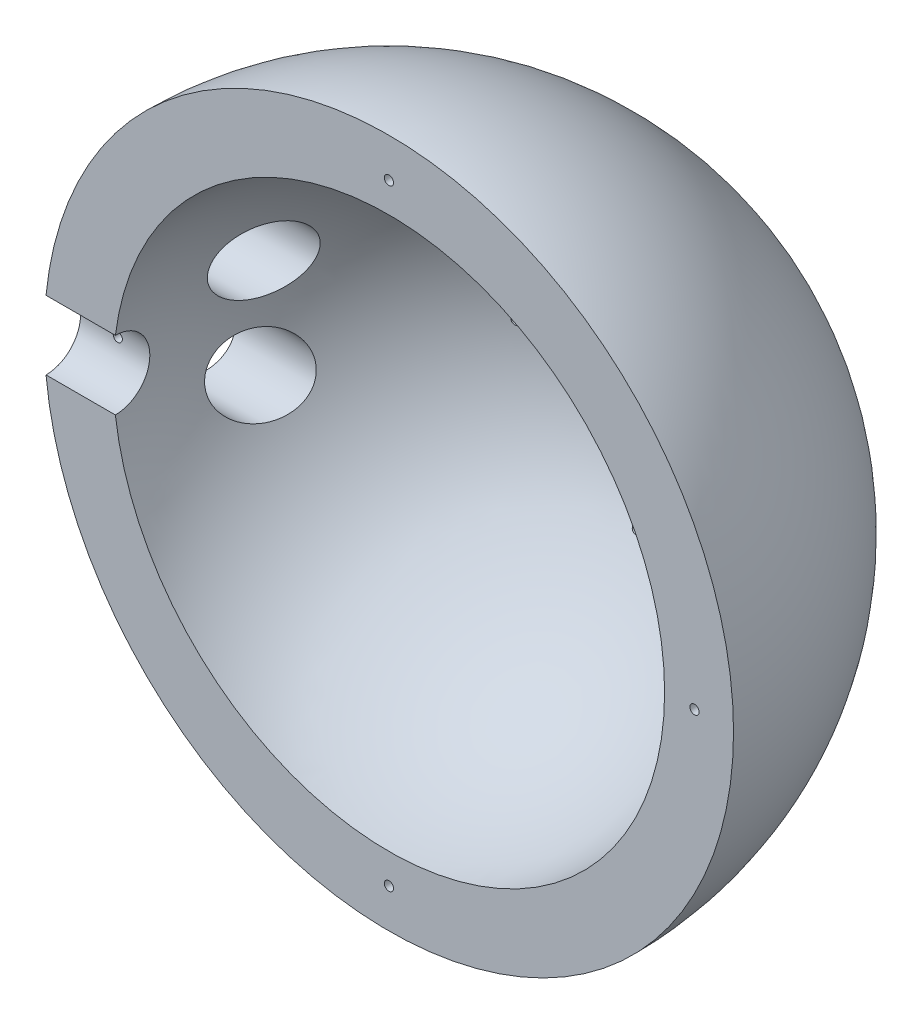
SolidWorks part; units mm, degrees
material "ABS"
ref_plane "Plano frontal" through (0, 0, 0) normal (0, 0, 1) x (1, 0, 0)
ref_plane "Plano superior" through (0, 0, 0) normal (0, 1, 0) x (1, 0, 0)
ref_plane "Plano direito" through (0, 0, 0) normal (1, 0, 0) x (0, 0, -1)
sketch "Esboço1" plane through (0, 0, 0) normal (0, 0, 1) x (1, 0, 0)
  line L0 (-60, 0) -> (-75, 0)
  line L1 (-60, 0) -> (-211.1575, 0) construction
  line L2 (75, 0) -> (60, 0)
  arc A0 (60, 0) -> (-60, 0) centre (0, 0) ccw
  arc A1 (75, 0) -> (-75, 0) centre (0, 0) ccw
  dimension "D1" = 120
  dimension "D2" = 150
revolve "Revolução1" add sketch "Esboço1" angle 180 about L1
ref_axis "Eixo1" through (0, 0, -70.0691) along (0, 0, 1)
sketch "Esboço6" plane through (0, 0, 0) normal (0, 0, 1) x (1, 0, 0)
  circle A0 centre (0, 0) radius 20
  dimension "D1" = 40
extrude "Corte-extrusão3" cut sketch "Esboço6" against normal through all
sketch "Esboço7" plane through (0, 0, 0) normal (1, 0, 0) x (0, 0, -1)
  circle A0 centre (0, 0) radius 7.5
  dimension "D1" = 15
extrude "Corte-extrusão4" cut sketch "Esboço7" against normal through all
sketch "Esboço8" plane through (0, 0, 0) normal (0, 1, 0) x (1, 0, 0)
  line L1 (-35, 79.2836) -> (35, 79.2836)
  line L2 (-35, 79.2836) -> (-35, 66.7325)
  line L3 (-35, 66.7325) -> (35, 66.7325)
  line L4 (35, 79.2836) -> (35, 66.7325)
  line L5 (-35, 79.2836) -> (35, 66.7325) construction
  line L6 (-35, 66.7325) -> (35, 79.2836) construction
  point P0 (0, 73.008)
  dimension "D1" = 0
  dimension "D2" = 70
extrude "Corte-extrusão5" cut sketch "Esboço8" against normal blind 44 and the other way blind 50
sketch "Esboço9" plane through (0, 0, -66.7325) normal (0, 0, -1) x (-1, 0, 0)
  line L0 (0, 34.2312) -> (0, 20) construction
  circle A0 centre (0, 0) radius 34.2312 construction
  circle A1 centre (0, 0) radius 20 construction
  circle A2 centre (-26, 0) radius 1
  circle A3 centre (0, 26) radius 1
  circle A4 centre (26, 0) radius 1
  circle A5 centre (0, -26) radius 1
  dimension "D1" = 14.2312
  dimension "D2" = 2
  dimension "D3" = 26
  dimension "D4" = 4
extrude "Corte-extrusão6" cut sketch "Esboço9" against normal through all
ref_plane "Plane1" through (-74.6241, 0, 0) normal (1, 0, 0) x (0, 0, -1)
sketch "Sketch2" plane through (-74.6241, 0, 0) normal (1, 0, 0) x (0, 0, -1)
  line L0 (0, 0) -> (60.8838, 0) construction
  line L1 (25, -24.0987) -> (25, 29.2491) construction
  circle A0 centre (25, -9.2962) radius 8.2
  circle A1 centre (25, 12.7) radius 8.2
  dimension "D3" = 16.4
  dimension "D4" = 16.4
  dimension "D1" = 9.2962
  dimension "D2" = 12.7
  dimension "D5" = 25
extrude "Cut-Extrude3" cut sketch "Sketch2" along normal blind 30
ref_plane "Plane2" through (0, 0, 10) normal (0, 0, 1) x (1, 0, 0)
sketch "Sketch4" plane through (0, 0, 10) normal (0, 0, 1) x (1, 0, 0)
  circle A0 centre (66.5, 0) radius 1
  circle A1 centre (0, -66.5) radius 1
  circle A2 centre (-66.5, 0) radius 1
  circle A3 centre (0, 66.5) radius 1
  point P12 (0, 0)
  dimension "D1" = 2
  dimension "D2" = 66.5
  dimension "D3" = 4
extrude "Cut-Extrude4" cut sketch "Sketch4" against normal blind 20
ref_plane "Plane3" through (0, 0, 0) normal (0, 0, 1) x (1, 0, 0)
